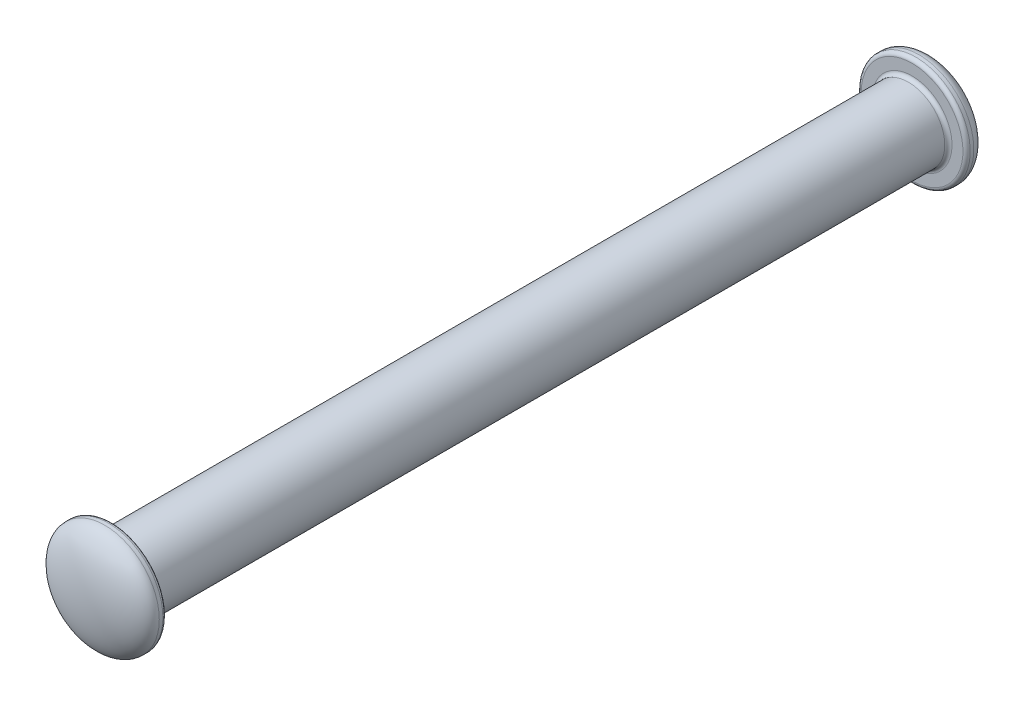
SolidWorks part; units mm, degrees
ref_plane "Front Plane" through (0, 0, 0) normal (0, 0, 1) x (1, 0, 0)
ref_plane "Top Plane" through (0, 0, 0) normal (0, 1, 0) x (1, 0, 0)
ref_plane "Right Plane" through (0, 0, 0) normal (1, 0, 0) x (0, 0, -1)
sketch "Sketch1" plane through (0, 0, 0) normal (0, 0, 1) x (1, 0, 0)
  circle A0 centre (0, 0) radius 0.5
  dimension "D1" = 1
extrude "Boss-Extrude1" add sketch "Sketch1" along normal blind 11
sketch "Sketch2" plane through (0, 0, 11) normal (0, 0, 1) x (1, 0, 0)
  circle A0 centre (0, 0) radius 0.75
  dimension "D1" = 1.5
extrude "Boss-Extrude2" add sketch "Sketch2" along normal blind 0.1
sketch "Sketch3" plane through (0, 0, 0) normal (0, 0, -1) x (-1, 0, 0)
  circle A0 centre (0, 0) radius 0.75
  dimension "D1" = 1.5
extrude "Boss-Extrude3" add sketch "Sketch3" along normal blind 0.1
dome "Dome1" faces to dome 1 distance 0.3 reverse direction no elliptical dome yes face at (-0.75, 0, -0.1) parameters "D1"=0.3
dome "Dome2" faces to dome 1 distance 0.3 reverse direction no elliptical dome yes face at (0.75, 0, 11.1) parameters "D1"=0.3
fillet "Fillet2" radius 0.05 4 edges at (0.5, 0, 11) (0.75, 0, 11) (-0.5, 0, 0) (-0.75, 0, 0)
